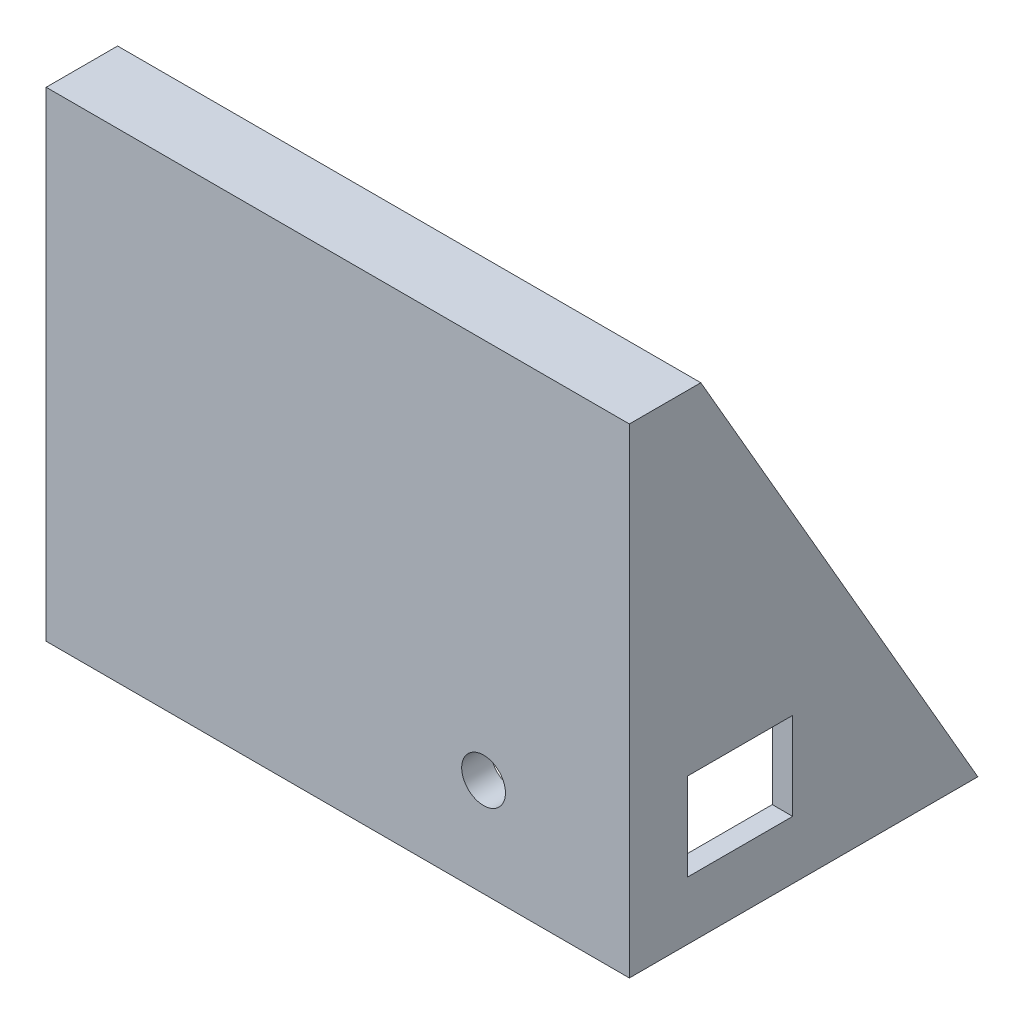
SolidWorks part; units mm, degrees
material "ABS"
ref_plane "Front Plane" through (0, 0, 0) normal (0, 0, 1) x (1, 0, 0)
ref_plane "Top Plane" through (0, 0, 0) normal (0, 1, 0) x (1, 0, 0)
ref_plane "Right Plane" through (0, 0, 0) normal (1, 0, 0) x (0, 0, -1)
sketch "Sketch2" plane through (0, 0, 0) normal (1, 0, 0) x (0, 0, -1)
  line L0 (0, 60.7895) -> (24.5, 60.7895)
  line L1 (24.5, 60.7895) -> (119.5, -103.7554)
  line L2 (119.5, -103.7554) -> (0, -103.7554)
  line L3 (0, -103.7554) -> (0, 60.7895)
  dimension "D1" = 24.5
  dimension "D2" = 190
  dimension "D3" = 120
extrude "Boss-Extrude1" add sketch "Sketch2" along normal blind 200
shell "Shell1" thickness 10 removed face at (100, -103.7554, -59.75)
sketch "Sketch4" plane through (0, 25.8062, -44.6976) normal (0, 0.5, -0.866) x (-1, 0, 0)
  line L0 (-200, 40.3952) -> (0, 40.3952) construction
  line L1 (-200, -149.6048) -> (-200, 40.3952) construction
  line L3 (0, -149.6048) -> (0, 40.3952) construction
  line L4 (-200, -149.6048) -> (0, -149.6048) construction
  circle A0 centre (-185, 0.3952) radius 2.5
  circle A1 centre (-185, -109.6048) radius 2.5
  circle A2 centre (-155, -139.6048) radius 2.5
  circle A3 centre (-45, -139.6048) radius 2.5
  circle A4 centre (-15, -109.6048) radius 2.5
  circle A5 centre (-15, 0.3952) radius 2.5
  circle A6 centre (-45, 30.3952) radius 2.5
  circle A7 centre (-155, 30.3952) radius 2.5
  dimension "D1" = 5
  dimension "D2" = 5
  dimension "D3" = 5
  dimension "D4" = 5
  dimension "D5" = 5
  dimension "D6" = 5
  dimension "D7" = 5
  dimension "D8" = 5
  dimension "D10" = 15
  dimension "D11" = 40
  dimension "D12" = 45
  dimension "D13" = 45
  dimension "D14" = 15
  dimension "D15" = 10
  dimension "D16" = 40
  dimension "D17" = 40
  dimension "D18" = 15
  dimension "D19" = 10
  dimension "D20" = 45
  dimension "D21" = 15
  dimension "D22" = 40
  dimension "D23" = 10
  dimension "D24" = 45
  dimension "D9" = 10
extrude "Cut-Extrude2" cut sketch "Sketch4" against normal blind 5
sketch "Sketch5" plane through (200, 0, 0) normal (1, 0, 0) x (0, 0, -1)
  line L0 (0, 60.7895) -> (0, -103.7554) construction
  line L1 (20, -53.7554) -> (56, -53.7554)
  line L2 (20, -53.7554) -> (20, -83.7554)
  line L3 (20, -83.7554) -> (56, -83.7554)
  line L4 (56, -53.7554) -> (56, -83.7554)
  line L5 (0, -103.7554) -> (119.5, -103.7554) construction
  point P6 (20, -68.7554)
  dimension "D1" = 36
  dimension "D2" = 30
  dimension "D3" = 20
  dimension "D4" = 20
extrude "Cut-Extrude3" cut sketch "Sketch5" against normal blind 20
sketch "Sketch6" plane through (0, 0, 0) normal (0, 0, 1) x (1, 0, 0)
  line L0 (200, 60.7895) -> (200, -103.7554) construction
  circle A0 centre (150, -70.0359) radius 7.5
  dimension "D1" = 15
  dimension "D2" = 50
extrude "Cut-Extrude4" cut sketch "Sketch6" against normal blind 20
